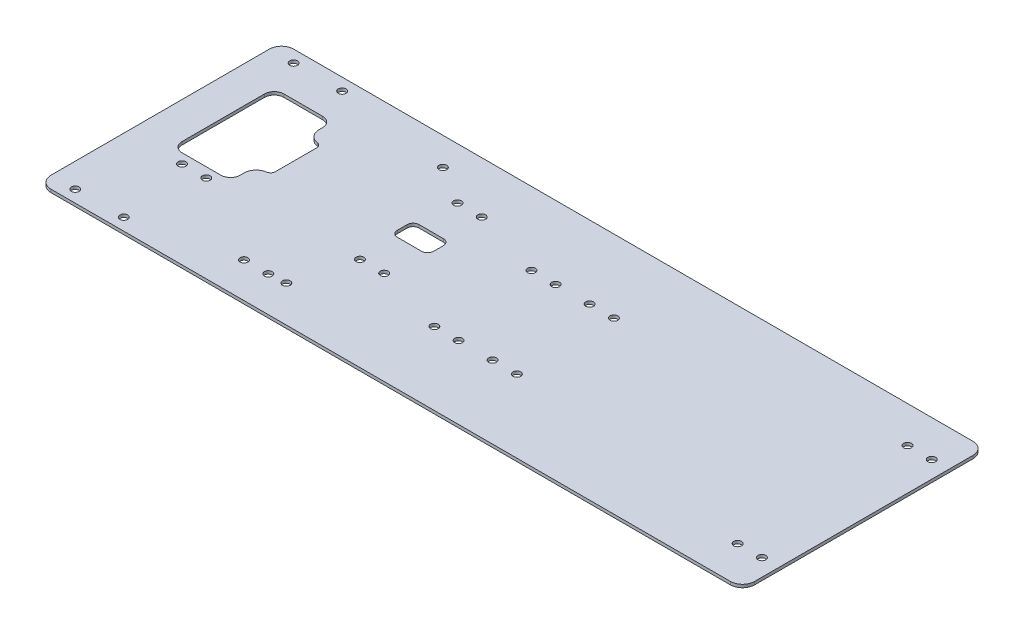
SolidWorks part; units mm, degrees
ref_plane "Front Plane" through (0, 0, 0) normal (0, 0, 1) x (1, 0, 0)
ref_plane "Top Plane" through (0, 0, 0) normal (0, 1, 0) x (1, 0, 0)
ref_plane "Right Plane" through (0, 0, 0) normal (1, 0, 0) x (0, 0, -1)
sketch "Sketch1" plane through (0, 0, 0) normal (0, 1, 0) x (1, 0, 0)
  line L0 (128.27, 0) -> (-128.27, 0) construction
  line L1 (184.15, 63.5) -> (-184.15, 63.5)
  line L2 (184.15, 63.5) -> (184.15, -63.5)
  line L3 (184.15, -63.5) -> (-184.15, -63.5)
  line L4 (-184.15, 63.5) -> (-184.15, -63.5)
  line L5 (184.15, 63.5) -> (-184.15, -63.5) construction
  line L6 (184.15, -63.5) -> (-184.15, 63.5) construction
  line L7 (-128.27, 0) -> (-128.27, 31.75) construction
  line L8 (-128.27, 31.75) -> (-134.62, 31.75) construction
  line L9 (-128.27, 6.35) -> (-134.62, 6.35) construction
  line L12 (-165.1, -12.7) -> (-165.1, 40.64)
  line L15 (-134.62, -12.7) -> (-165.1, -12.7)
  line L17 (-134.62, 40.64) -> (-165.1, 40.64)
  line L18 (0, 63.5) -> (0, -63.5) construction
  line L19 (-134.62, 40.64) -> (-134.62, -12.7)
  line L21 (-95.25, -45.0215) -> (-95.25, -32.3215) construction
  line L22 (-82.55, -45.0215) -> (-95.25, -45.0215) construction
  line L25 (128.27, 31.75) -> (128.27, 6.35) construction
  line L26 (-95.25, -32.3215) -> (-82.55, -32.3215) construction
  line L30 (-82.55, -32.3215) -> (-82.55, -45.0215) construction
  line L31 (184.15, -17.78) -> (154.94, -17.78) construction
  line L32 (146.05, 57.15) -> (184.15, 57.15) construction
  line L33 (154.94, -17.78) -> (142.24, -17.78) construction
  line L34 (146.05, -57.15) -> (184.15, -57.15) construction
  line L35 (-146.05, -57.15) -> (-184.15, -57.15) construction
  line L36 (-146.05, 57.15) -> (-184.15, 57.15) construction
  line L37 (-128.27, 0) -> (-128.27, 6.35) construction
  line L38 (-184.15, -17.78) -> (-154.94, -17.78) construction
  line L39 (-154.94, -17.78) -> (-142.24, -17.78) construction
  line L40 (-134.62, 27.305) -> (-127, 27.305)
  line L41 (-127, 27.305) -> (-127, 0.635)
  line L42 (-127, 0.635) -> (-134.62, 0.635)
  circle A4 centre (171.45, 31.75) radius 2.032 construction
  circle A5 centre (128.27, 31.75) radius 2.032 construction
  circle A6 centre (128.27, 6.35) radius 2.032 construction
  circle A7 centre (171.45, -3.81) radius 2.032 construction
  circle A8 centre (171.45, -57.15) radius 2.032
  circle A9 centre (146.05, -57.15) radius 2.032
  circle A10 centre (171.45, 57.15) radius 2.032
  circle A11 centre (146.05, 57.15) radius 2.032
  circle A12 centre (-146.05, -57.15) radius 2.032
  circle A13 centre (-171.45, -57.15) radius 2.032
  circle A14 centre (-146.05, 57.15) radius 2.032
  circle A15 centre (-171.45, 57.15) radius 2.032
  circle A16 centre (142.24, -17.78) radius 2.032 construction
  circle A17 centre (154.94, -17.78) radius 2.032 construction
  circle A18 centre (-154.94, -17.78) radius 2.032
  circle A19 centre (-142.24, -17.78) radius 2.032
  circle A20 centre (-95.25, -45.0215) radius 2.032
  circle A21 centre (-82.55, -45.0215) radius 2.032
  circle A22 centre (-95.25, -32.3215) radius 2.032
  circle A23 centre (-82.55, -32.3215) radius 2.032
  point P0 (0, 0)
  point P11 (-128.27, 0)
  point P13 (-134.62, 31.75)
  point P17 (-134.62, 6.35)
  point P37 (0, 0)
  point P50 (171.45, 57.15)
  point P51 (146.05, 57.15)
  point P56 (171.45, -57.15)
  point P57 (146.05, -57.15)
  point P84 (-130.81, 27.305)
  point P87 (130.81, 27.305)
  dimension "D5" = 13.335
  dimension "D18" = 4.064
  dimension "D1" = 368.3
  dimension "D2" = 127
  dimension "D3" = 128.27
  dimension "D4" = 25.4
  dimension "D7" = 6.35
  dimension "D8" = 30.48
  dimension "D9" = 53.34
  dimension "D10" = 8.89
  dimension "D11" = 19.05
  dimension "D14" = 12.7
  dimension "D15" = 38.1
  dimension "D16" = 12.7
  dimension "D17" = 38.1
  dimension "D19" = 31.75
  dimension "D20" = 6.35
  dimension "D21" = 6.35
  dimension "D22" = 5.08
  dimension "D23" = 29.21
  dimension "D24" = 12.7
  dimension "D25" = 88.9
  dimension "D26" = 12.7
  dimension "D27" = 7.62
  dimension "D28" = 26.67
  dimension "D29" = 13.335
  dimension "D30" = 18.4785
  dimension "D31" = 12.7
extrude "Boss-Extrude1" add sketch "Sketch1" along normal blind 1.5875 contours L1 L4 L3 L2 A23 A22 A21 A20 A18 A14 A12 A11 A10 A9 A8 L41 L42 L19 L15 L12 L17 L40 A13 A15 A19 | A9 | A8 | A11 | A10 | A22 | A23 region at (6.2259, 0, 0.5157) region at (171.45, 0, 57.15) region at (146.05, 0, 57.15) region at (171.45, 0, -57.15) region at (146.05, 0, -57.15) region at (-95.25, 0, 32.3215) region at (-82.55, 0, 32.3215)
sketch "Sketch2" [suppressed] plane through (0, 1.5875, 0) normal (0, 1, 0) x (1, 0, 0)
  line L0 (-69.85, 63.5) -> (-69.85, -63.5)
  line L1 (184.15, 63.5) -> (-184.15, 63.5) construction
  line L2 (184.15, -63.5) -> (-184.15, -63.5) construction
  circle A0 centre (-82.55, -45.0215) radius 2.032 construction
  circle M9 centre (146.05, 57.15) radius 2.032
  circle M10 centre (171.45, 57.15) radius 2.032
  circle M11 centre (146.05, -57.15) radius 2.032
  circle M12 centre (171.45, -57.15) radius 2.032
  line M13 (184.15, 63.5) -> (-184.15, 63.5)
  line M15 (-184.15, -63.5) -> (184.15, -63.5)
  line M16 (184.15, -63.5) -> (184.15, 63.5)
  dimension "D1" = 12.7
extrude "Cut-Extrude1" [suppressed] cut sketch "Sketch2" against normal through all flip side to cut contours L0 M13 M15 M16 M10 M12 M11 M9
fillet "Fillet1" radius 5.08 4 edges at (-134.62, 0.7937, 12.7) (-165.1, 0.7937, 12.7) (-165.1, 0.7937, -40.64) (-134.62, 0.7937, -40.64)
fillet "Fillet3" radius 6.35 4 edges at (184.15, 0.7937, 63.5) (184.15, 0.7937, -63.5) (-184.15, 0.7937, 63.5) (-184.15, 0.7937, -63.5)
fillet "Fillet4" radius 2.54 2 edges at (-127, 0.7937, -0.635) (-127, 0.7937, -27.305)
fillet "Fillet5" radius 6.35 2 edges at (-134.62, 0.7937, -0.635) (-134.62, 0.7937, -27.305)
fillet "Fillet6" [suppressed] radius 6.35
sketch "Sketch3" plane through (0, 1.5875, 0) normal (0, 1, 0) x (1, 0, 0)
  circle A0 centre (25.4, -25.4) radius 2.032
  circle A1 centre (25.4, 25.4) radius 2.032
  arc A2 (10.7648, -26.0196) -> (10.7648, -24.7804) centre (12.7, -25.4) ccw construction
  circle A3 centre (25.4, -25.4) radius 2.032 construction
  circle A4 centre (25.4, 25.4) radius 2.032 construction
  arc A5 (10.7648, 24.7804) -> (10.7648, 26.0196) centre (12.7, 25.4) ccw construction
  arc A6 (10.7648, 24.7804) -> (10.7648, 26.0196) centre (12.7, 25.4) ccw
  arc A7 (10.7648, -26.0196) -> (10.7648, -24.7804) centre (12.7, -25.4) ccw
  circle A9 centre (162.56, -44.45) radius 2.032 construction
  circle A10 centre (162.56, 44.45) radius 2.032 construction
  circle A12 centre (-2.54, -25.4) radius 2.032 construction
  circle A15 centre (-73.66, 44.45) radius 2.032 construction
  circle A16 centre (-73.66, -44.45) radius 2.032 construction
  circle A17 centre (25.4, -25.4) radius 2.032
  circle A18 centre (25.4, 25.4) radius 2.032
  circle A19 centre (-15.24, -25.4) radius 2.032 construction
  circle A20 centre (-15.24, 25.4) radius 2.032 construction
  circle A23 centre (162.56, -44.45) radius 2.032
  circle A24 centre (162.56, 44.45) radius 2.032
  circle A29 centre (12.7, -25.4) radius 2.032
  circle A31 centre (12.7, 25.4) radius 2.032
  circle A32 centre (175.26, 44.45) radius 2.032 construction
  circle A33 centre (175.26, -44.45) radius 2.032 construction
  circle A34 centre (175.26, 44.45) radius 2.032
  circle A35 centre (175.26, -44.45) radius 2.032
  circle A36 centre (-2.54, 25.4) radius 2.032 construction
  circle A41 centre (-2.54, -25.4) radius 2.032
  circle A42 centre (-2.54, 25.4) radius 2.032
  circle A54 centre (-73.66, 44.45) radius 2.032
  circle A55 centre (-73.66, -44.45) radius 2.032
  circle A56 centre (-15.24, -25.4) radius 2.032
  circle A57 centre (-15.24, 25.4) radius 2.032
extrude "Cut-Extrude5" [suppressed] cut sketch "Sketch3" against normal through all contours A55 | A54 | A57 | A56 | A41 | A0 | A42 | A31 | A29 | A1
sketch "Sketch4" plane through (0, 1.5875, 0) normal (0, 1, 0) x (1, 0, 0)
  line L0 (-50.9125, -11.9075) -> (-66.7875, -11.9075) construction
  line L1 (-66.7875, -17.0193) -> (-50.9125, -17.0193) construction
  line L2 (-66.7875, 38.758) -> (-50.9125, 38.758) construction
  line L3 (-50.9125, 34.44) -> (-66.7875, 34.44) construction
  line L4 (-50.9125, -11.9075) -> (-66.7875, -11.9075)
  line L5 (-66.7875, -17.0193) -> (-50.9125, -17.0193)
  line L6 (-66.7875, 38.758) -> (-50.9125, 38.758)
  line L7 (-50.9125, 34.44) -> (-66.7875, 34.44)
  line L8 (-66.7875, 36.599) -> (-50.9125, 36.599) construction
  line L9 (-66.7875, -14.4634) -> (-50.9125, -14.4634) construction
  arc A0 (-50.9125, -17.0193) -> (-50.9125, -11.9075) centre (-50.9125, -14.4634) ccw construction
  arc A1 (-66.7875, -11.9075) -> (-66.7875, -17.0193) centre (-66.7875, -14.4634) ccw construction
  arc A3 (-66.7875, 38.758) -> (-66.7875, 34.44) centre (-66.7875, 36.599) ccw construction
  arc A4 (-50.9125, -17.0193) -> (-50.9125, -11.9075) centre (-50.9125, -14.4634) ccw
  arc A5 (-66.7875, -11.9075) -> (-66.7875, -17.0193) centre (-66.7875, -14.4634) ccw
  arc A6 (-50.9125, 34.44) -> (-50.9125, 38.758) centre (-50.9125, 36.599) ccw construction
  arc A7 (-66.7875, 38.758) -> (-66.7875, 34.44) centre (-66.7875, 36.599) ccw
  arc A8 (-50.9125, 34.44) -> (-50.9125, 38.758) centre (-50.9125, 36.599) ccw
  circle A9 centre (-65.1365, 36.599) radius 2.032
  circle A10 centre (-52.4365, 36.599) radius 2.032
  circle A11 centre (-65.1365, -14.4634) radius 2.032
  circle A12 centre (-52.4365, -14.4634) radius 2.032
  dimension "D1" = 4.064
  dimension "D2" = 12.7
  dimension "D3" = 1.651
  dimension "D4" = 12.7
  dimension "D5" = 1.651
extrude "Cut-Extrude6" cut sketch "Sketch4" against normal through all and the other way through all contours A11 | A12 | A10 | A9 region at (-65.1365, 1.5875, -36.599) region at (-52.4365, 1.5875, -36.599) region at (-65.1365, 1.5875, 14.4634) region at (-52.4365, 1.5875, 14.4634)
sketch "Sketch5" plane through (0, 1.5875, 0) normal (0, 1, 0) x (1, 0, 0)
  line L1 (-67.175, 12.0678) -> (-67.175, 10.0678) construction
  line L3 (-67.175, 12.0678) -> (-67.175, 10.0678)
  line L4 (-65.375, 13.8678) -> (-52.675, 13.8678)
  line L5 (-65.375, 8.2678) -> (-52.675, 8.2678)
  line L6 (-50.8769, 10.013) -> (-50.8769, 12.0776)
  line L8 (-65.375, 13.6053) -> (-65.375, 8.5253) construction
  line L9 (-62.2, 13.6053) -> (-62.2, 8.5253)
  line L10 (-68.55, 13.6053) -> (-68.55, 8.5253)
  line L11 (-65.375, 6.9978) -> (-52.6746, 6.9978)
  line L12 (-49.6069, 9.9962) -> (-49.6069, 12.0806)
  line L13 (-65.375, 15.1378) -> (-52.6743, 15.1378)
  line L14 (-68.445, 12.0678) -> (-68.445, 10.0678)
  line L15 (-52.675, 13.5878) -> (-52.675, 8.5078) construction
  line L16 (-49.5, 13.5878) -> (-49.5, 8.5078)
  line L17 (-55.85, 13.5878) -> (-55.85, 8.5078)
  line L18 (-67.175, 11.0678) -> (-50.8769, 11.0453) construction
  line L20 (-65.375, 16.7803) -> (-52.675, 16.7628)
  line L22 (-52.675, 5.3328) -> (-65.375, 5.3503)
  arc A0 (-63.575, 12.0678) -> (-67.175, 12.0678) centre (-65.375, 12.0678) ccw construction
  arc A2 (-67.175, 10.0678) -> (-65.375, 8.2678) centre (-65.375, 10.0678) ccw construction
  arc A3 (-65.375, 13.8678) -> (-67.175, 12.0678) centre (-65.375, 12.0678) ccw
  arc A5 (-67.175, 10.0678) -> (-65.375, 8.2678) centre (-65.375, 10.0678) ccw
  arc A6 (-50.8769, 12.0776) -> (-52.675, 13.8678) centre (-52.6769, 12.0678) ccw
  arc A7 (-52.675, 8.2678) -> (-50.8769, 10.013) centre (-52.6761, 10.0678) ccw
  arc A9 (-62.2, 13.6053) -> (-68.55, 13.6053) centre (-65.375, 13.6053) ccw
  arc A10 (-68.55, 8.5253) -> (-62.2, 8.5253) centre (-65.375, 8.5253) ccw
  arc A11 (-49.5, 13.5878) -> (-55.85, 13.5878) centre (-52.675, 13.5878) ccw
  arc A12 (-52.6746, 6.9978) -> (-49.6069, 9.9962) centre (-52.6761, 10.0678) ccw
  arc A13 (-49.6069, 12.0806) -> (-52.6743, 15.1378) centre (-52.6769, 12.0678) ccw
  arc A14 (-65.375, 15.1378) -> (-68.445, 12.0678) centre (-65.375, 12.0678) ccw
  arc A15 (-68.445, 10.0678) -> (-65.375, 6.9978) centre (-65.375, 10.0678) ccw
  arc A16 (-55.85, 8.5078) -> (-49.5, 8.5078) centre (-52.675, 8.5078) ccw
  point P17 (-65.375, 11.0653)
  point P22 (-52.675, 11.0478)
  dimension "D1" = 16.2981
  dimension "D2" = 12.7
  dimension "D3" = 2.0646
  dimension "D4" = 1.7902
  dimension "D5" = 5.08
  dimension "D7" = 3.175
  dimension "D6" = 1.27
extrude "Cut-Extrude7" cut sketch "Sketch5" against normal through all and the other way through all contours A16 L11 A10 L22 | A16 L5 A10 L11 | A16 L17 A11 L4 A9 L9 A10 L5 | A11 L13 A9 L4 | A11 L20 A9 L13 | A9 L10 A10 L9 | A16 L16 A11 L17 region at (-59.0223, 1.5875, -14.515) region at (-59.025, 1.5875, -11.0679) region at (-59.0276, 1.5875, -7.621) region at (-63.9847, 1.5875, -15.3335) region at (-59.0255, 1.5875, -6.1024)
sketch "Sketch6" plane through (0, 1.5875, 0) normal (0, 1, 0) x (1, 0, 0)
  circle A0 centre (-85.09, 48.895) radius 2.032 construction
  circle A1 centre (-73.66, -44.45) radius 2.032 construction
  circle A2 centre (-2.54, -25.4) radius 2.032 construction
  circle A3 centre (-15.24, -25.4) radius 2.032 construction
  circle A4 centre (-15.24, 25.4) radius 2.032 construction
  circle A5 centre (-2.54, 25.4) radius 2.032 construction
  circle A6 centre (15.24, 25.4) radius 2.032 construction
  circle A7 centre (27.94, 25.4) radius 2.032 construction
  circle A8 centre (15.24, -25.4) radius 2.032 construction
  circle A9 centre (27.94, -25.4) radius 2.032 construction
  circle A10 centre (175.26, 44.45) radius 2.032 construction
  circle A11 centre (162.56, 44.45) radius 2.032 construction
  circle A12 centre (175.26, -44.45) radius 2.032 construction
  circle A13 centre (162.56, -44.45) radius 2.032 construction
  circle A14 centre (-85.09, 48.895) radius 2.032
  circle A15 centre (-73.66, -44.45) radius 2.032
  circle A16 centre (-2.54, -25.4) radius 2.032
  circle A17 centre (-15.24, -25.4) radius 2.032
  circle A18 centre (-15.24, 25.4) radius 2.032
  circle A19 centre (-2.54, 25.4) radius 2.032
  circle A20 centre (15.24, 25.4) radius 2.032
  circle A21 centre (27.94, 25.4) radius 2.032
  circle A22 centre (15.24, -25.4) radius 2.032
  circle A23 centre (27.94, -25.4) radius 2.032
  circle A24 centre (175.26, 44.45) radius 2.032
  circle A25 centre (162.56, 44.45) radius 2.032
  circle A26 centre (175.26, -44.45) radius 2.032
  circle A27 centre (162.56, -44.45) radius 2.032
extrude "Cut-Extrude8" cut sketch "Sketch6" against normal through all contours A14 | A15 | A17 | A18 | A19 | A16 | A22 | A20 | A21 | A23 | A25 | A24 | A27 | A26
equation "\".80.55in\"=0.55"
